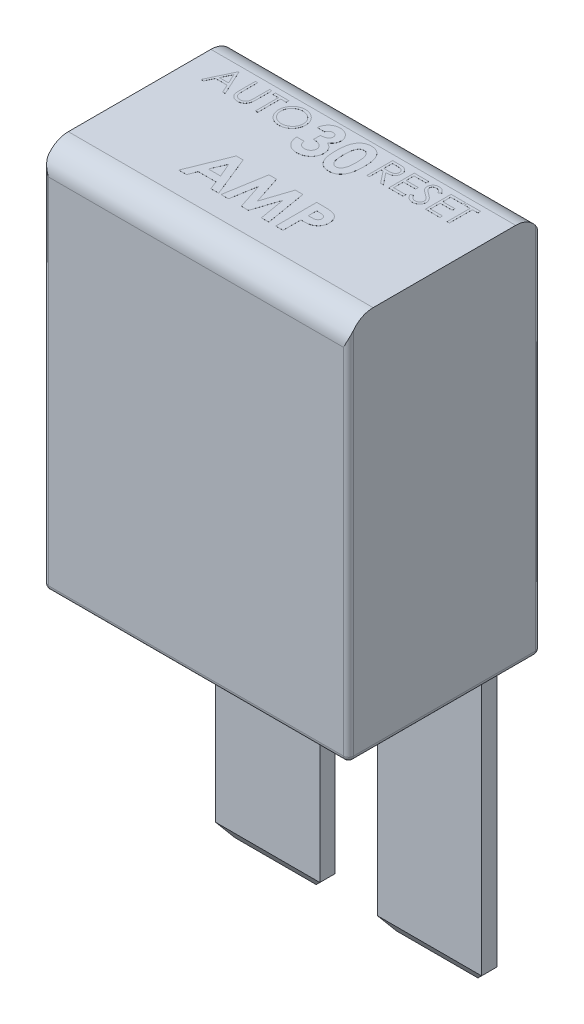
SolidWorks part; units mm, degrees
material "Free-Cutting Brass, UNS C36000"
ref_plane "Front Plane" through (0, 0, 0) normal (0, 0, 1) x (1, 0, 0)
ref_plane "Top Plane" through (0, 0, 0) normal (0, 1, 0) x (1, 0, 0)
ref_plane "Right Plane" through (0, 0, 0) normal (1, 0, 0) x (0, 0, -1)
sketch "Sketch1" plane through (0, 0, 0) normal (0, 1, 0) x (1, 0, 0)
  line L5 (-7.874, -4.953) -> (7.874, -4.953)
  line L6 (-7.874, -4.953) -> (-7.874, 4.953)
  line L7 (-7.874, 4.953) -> (7.874, 4.953)
  line L8 (7.874, -4.953) -> (7.874, 4.953)
  line L9 (-7.874, -4.953) -> (7.874, 4.953) construction
  line L10 (-7.874, 4.953) -> (7.874, -4.953) construction
  point P4 (0, 0)
  dimension "D3" = 9.906
  dimension "D4" = 15.748
extrude "Extrude1" add sketch "Sketch1" along normal blind 19.812
fillet "Fillet1" radius 1.27 2 edges at (0, 19.812, -4.953) (0, 19.812, 4.953)
fillet "Fillet2" radius 0.254 8 edges at (7.874, 9.271, -4.953) (-7.874, 9.271, -4.953) (0, 0, -4.953) (-7.874, 0, 0) (0, 0, 4.953) (7.874, 0, 0) (-7.874, 9.271, 4.953) (7.874, 9.271, 4.953) tangent propagation no
sketch "Sketch2" plane through (0, 0, 0) normal (0, -1, 0) x (1, 0, 0)
  line L0 (-1.4859, -2.9261) -> (-6.8707, -2.9261)
  line L1 (-6.8707, -2.9261) -> (-6.8707, -3.7135)
  line L2 (-6.8707, -3.7135) -> (-1.4859, -3.7135)
  line L3 (-1.4859, -3.7135) -> (-1.4859, -2.9261)
  line L4 (7.62, -4.953) -> (-7.62, -4.953) construction
  line L5 (-7.874, -4.699) -> (-7.874, 4.699) construction
  dimension "D1" = 5.3848
  dimension "D2" = 0.7874
  dimension "D3" = 1.2395
  dimension "D4" = 1.0033
extrude "Extrude2" add sketch "Sketch2" along normal blind 14.478
chamfer "Chamfer1" distance 0.5842 angle 45 2 edges at (-6.8707, -14.478, -3.3198) (-1.4859, -14.478, -3.3198)
chamfer "Chamfer2" distance 0.5842 angle 34 2 edges at (-4.1783, -14.478, -3.7135) (-4.1783, -14.478, -2.9261) first distance on face at (-4.1783, -9.4573, -3.7135) first distance on face at (-4.1783, -9.4573, -2.9261)
mirror "Mirror1" about plane through (0, 0, 0) normal (1, 0, 0) of "Chamfer2", "Chamfer1", "Extrude2"
sketch "Sketch3" plane through (0, 19.812, 0) normal (0, 1, 0) x (1, 0, 0)
  line L0 (-7.874, 3.683) -> (-7.874, -3.683) construction
  line L1 (-7.874, -3.683) -> (7.874, -3.683) construction
  text T0 "AUTO       RESET\r\n\r\n" font "Century Gothic" height in points 5
  text T1 "<b>30</b>\r\n" font "Century Gothic" height in points 8
  text T2 "<b>AMP</b>" font "Century Gothic" height in points 8
  dimension "D1" = 1.0253
  dimension "D2" = 4.5342
  dimension "D3" = 6.0571
  dimension "D4" = 1.1319
  dimension "D5" = 5.0109
  dimension "D6" = 5.7581
extrude "Extrude3" add sketch "Sketch3" along normal blind 0.0025
